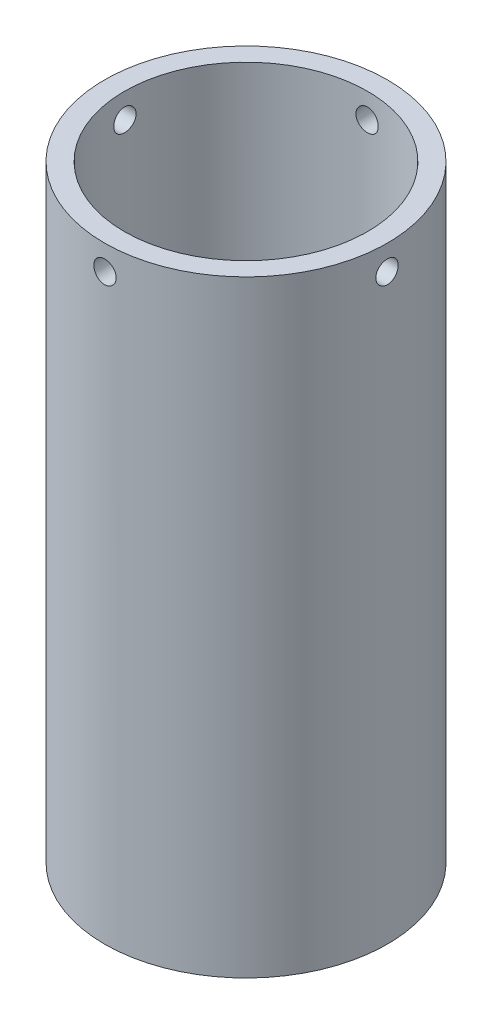
SolidWorks part; units mm, degrees
ref_plane "Front Plane" through (0, 0, 0) normal (0, 0, 1) x (1, 0, 0)
ref_plane "Top Plane" through (0, 0, 0) normal (0, 1, 0) x (1, 0, 0)
ref_plane "Right Plane" through (0, 0, 0) normal (1, 0, 0) x (0, 0, -1)
sketch "Sketch1" plane through (0, 0, 0) normal (0, 1, 0) x (1, 0, 0)
  circle A0 centre (0, 0) radius 28.5
  circle A1 centre (0, 0) radius 21
  dimension "D1" = 57
  dimension "D2" = 42
extrude "Boss-Extrude1" add sketch "Sketch1" along normal mid plane 121.35
sketch "Sketch2" plane through (0, 0, 0) normal (0, 0, 1) x (1, 0, 0)
  line L3 (21, 60.675) -> (-21, 60.675) construction
  circle A0 centre (0, 55.675) radius 2.25
  dimension "D1" = 4.5
  dimension "D2" = 5
extrude "Cut-Extrude1" cut sketch "Sketch2" against normal through all
pattern_circular "CirPattern1" count 4 every 90 about axis through (0, 60.675, 0) along (0, -1, 0) of "Cut-Extrude1"
sketch "Sketch5" plane through (0, -60.675, 0) normal (0, -1, 0) x (1, 0, 0)
  circle A0 centre (0, 0) radius 28.5 construction
  circle A1 centre (0, 0) radius 28.5
extrude "Cut-Extrude4" cut sketch "Sketch5" against normal blind 1
sketch "Sketch3" plane through (0, -59.675, 0) normal (0, -1, 0) x (1, 0, 0)
  line L0 (0, 28.5) -> (0, 21) construction
  circle A0 centre (0, -24.75) radius 2.25
  arc A1 (2.25, 20.8791) -> (-2.25, 20.8791) centre (0, 0) ccw construction
  circle A2 centre (0, 24.75) radius 2.25
  circle A3 centre (17.5009, 17.5009) radius 2.25
  circle A4 centre (24.75, 0) radius 2.25
  circle A5 centre (17.5009, -17.5009) radius 2.25
  circle A6 centre (0, 0) radius 28.5 construction
  circle A7 centre (-17.5009, -17.5009) radius 2.25
  circle A8 centre (-24.75, 0) radius 2.25
  circle A9 centre (-17.5009, 17.5009) radius 2.25
  point P19 (0, 0)
  dimension "D1" = 4.5
  dimension "D2" = 8
extrude "Cut-Extrude2" cut sketch "Sketch3" against normal blind 6.5
sketch "Sketch4" plane through (0, 60.675, 0) normal (0, 1, 0) x (1, 0, 0)
  line L0 (0, 24.5) -> (0, 28.5) construction
  circle A0 centre (0, 0) radius 24.5
  circle A1 centre (0, 0) radius 28.5 construction
  dimension "D1" = 4
extrude "Cut-Extrude3" cut sketch "Sketch4" against normal offset from surface (109.85 mm away) 4 up to face at (24.75, -53.175, -2.25)
sketch "Sketch7" plane through (0, -59.675, 0) normal (0, -1, 0) x (1, 0, 0)
  circle A0 centre (-17.5009, -17.5009) radius 2.25 construction
  circle A1 centre (0, -24.75) radius 2.25 construction
  circle A2 centre (17.5009, -17.5009) radius 2.25 construction
  circle A3 centre (24.75, 0) radius 2.25 construction
  circle A4 centre (-24.75, 0) radius 2.25 construction
  circle A5 centre (-17.5009, 17.5009) radius 2.25 construction
  circle A6 centre (0, 24.75) radius 2.25 construction
  circle A7 centre (17.5009, 17.5009) radius 2.25 construction
  circle A8 centre (0, 0) radius 28.5 construction
  circle A9 centre (0, 0) radius 21 construction
  circle A10 centre (-17.5009, -17.5009) radius 2.25
  circle A11 centre (0, -24.75) radius 2.25
  circle A12 centre (17.5009, -17.5009) radius 2.25
  circle A13 centre (24.75, 0) radius 2.25
  circle A14 centre (-24.75, 0) radius 2.25
  circle A15 centre (-17.5009, 17.5009) radius 2.25
  circle A16 centre (0, 24.75) radius 2.25
  circle A17 centre (17.5009, 17.5009) radius 2.25
  circle A18 centre (0, 0) radius 28.5
  circle A19 centre (0, 0) radius 21
extrude "Boss-Extrude2" add sketch "Sketch7" along normal blind 2
